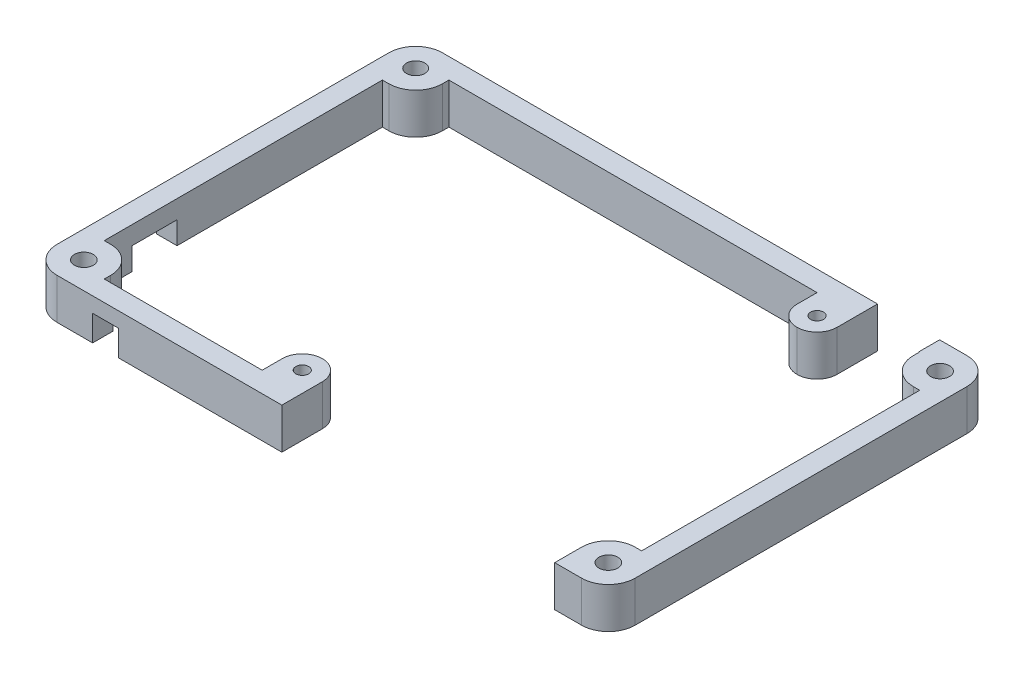
SolidWorks part; units mm, degrees
material "Rubber"
ref_plane "Front" through (0, 0, 0) normal (0, 0, 1) x (1, 0, 0)
ref_plane "Top" through (0, 0, 0) normal (0, 1, 0) x (1, 0, 0)
ref_plane "Right" through (0, 0, 0) normal (1, 0, 0) x (0, 0, -1)
sketch "Sketch1" plane through (0, 0, 0) normal (0, 1, 0) x (1, 0, 0)
  line L0 (-45, 0) -> (45, 0) construction
  line L1 (-45, 30) -> (45, 30) construction
  line L2 (-45, 30) -> (-45, -30) construction
  line L3 (-45, -30) -> (45, -30) construction
  line L4 (45, 30) -> (45, -30) construction
  line L5 (0, -30) -> (0, 30) construction
  line L6 (41.825, 26.825) -> (41.825, -26.825) construction
  line L7 (-41.825, -26.825) -> (41.825, -26.825) construction
  line L8 (-41.825, 26.825) -> (-41.825, -26.825) construction
  line L9 (-41.825, 26.825) -> (41.825, 26.825) construction
  line L10 (40.825, 25.825) -> (40.825, -25.825) construction
  line L11 (-40.825, -25.825) -> (40.825, -25.825) construction
  line L12 (-40.825, 25.825) -> (-40.825, -25.825) construction
  line L13 (-40.825, 25.825) -> (40.825, 25.825) construction
  line L14 (40.825, 21.65) -> (45, 21.65) construction
  line L15 (40.825, -21.65) -> (45, -21.65) construction
  line L16 (36.65, -25.825) -> (36.65, -30) construction
  line L17 (-36.65, -25.825) -> (-36.65, -30) construction
  line L18 (-40.825, -21.65) -> (-45, -21.65) construction
  line L19 (-36.65, 25.825) -> (-36.65, 30) construction
  line L20 (-40.825, 21.65) -> (-45, 21.65) construction
  line L21 (36.65, 25.825) -> (36.65, 30) construction
  line L22 (40.825, -25.825) -> (41.825, -25.825) construction
  circle A0 centre (-40.825, -25.825) radius 1 construction
  circle A1 centre (40.825, -25.825) radius 1 construction
  circle A2 centre (40.825, 25.825) radius 1 construction
  circle A3 centre (-40.825, 25.825) radius 1 construction
  circle A4 centre (40.825, -25.825) radius 4.175 construction
  circle A5 centre (40.825, 25.825) radius 4.175 construction
  circle A6 centre (-40.825, 25.825) radius 4.175 construction
  circle A7 centre (-40.825, -25.825) radius 4.175 construction
  dimension "D1" = 90
  dimension "D2" = 60
  dimension "D4" = 1
  dimension "D3" = 3.175
sketch "Sketch2" plane through (0, 0, 0) normal (0, 1, 0) x (1, 0, 0)
  line L0 (-45, 30) -> (-45, -30) construction
  line L1 (-45, -30) -> (45, -30) construction
  line L2 (45, 30) -> (45, -30) construction
  line L3 (-45, 30) -> (45, 30) construction
  line L4 (40.825, 21.65) -> (45, 21.65) construction
  line L5 (36.65, 25.825) -> (36.65, 30) construction
  line L6 (-36.65, 25.825) -> (-36.65, 30) construction
  line L7 (-40.825, 21.65) -> (-45, 21.65) construction
  line L8 (-36.65, -25.825) -> (-36.65, -30) construction
  line L9 (-40.825, -21.65) -> (-45, -21.65) construction
  line L10 (36.65, -25.825) -> (36.65, -30) construction
  line L11 (40.825, -21.65) -> (45, -21.65) construction
  line L16 (-45, 25.825) -> (-45, -25.825)
  line L17 (-40.825, -30) -> (40.825, -30)
  line L18 (45, 25.825) -> (45, -25.825)
  line L19 (-40.825, 30) -> (40.825, 30)
  line L20 (40.825, 21.65) -> (41.825, 21.65)
  line L21 (36.65, 25.825) -> (36.65, 26.825)
  line L22 (-36.65, 25.825) -> (-36.65, 26.825)
  line L23 (-40.825, 21.65) -> (-41.825, 21.65)
  line L24 (-36.65, -25.825) -> (-36.65, -26.825)
  line L25 (-40.825, -21.65) -> (-41.825, -21.65)
  line L26 (36.65, -25.825) -> (36.65, -26.825)
  line L27 (40.825, -21.65) -> (41.825, -21.65)
  line L28 (41.825, 26.825) -> (41.825, -26.825) construction
  line L29 (-36.65, -26.825) -> (36.65, -26.825)
  line L30 (-41.825, 26.825) -> (41.825, 26.825) construction
  line L31 (-41.825, 26.825) -> (-41.825, -26.825) construction
  line L32 (-36.65, 26.825) -> (36.65, 26.825)
  line L33 (-41.825, 21.65) -> (-41.825, -21.65)
  line L34 (41.825, 21.65) -> (41.825, -21.65)
  line L35 (-41.825, -26.825) -> (41.825, -26.825) construction
  circle A0 centre (40.825, 25.825) radius 4.175 construction
  circle A1 centre (40.825, 25.825) radius 1 construction
  circle A2 centre (-40.825, 25.825) radius 4.175 construction
  circle A3 centre (-40.825, 25.825) radius 1 construction
  circle A4 centre (-40.825, -25.825) radius 4.175 construction
  circle A5 centre (40.825, -25.825) radius 4.175 construction
  arc A6 (45, 25.825) -> (40.825, 30) centre (40.825, 25.825) ccw
  circle A7 centre (40.825, 25.825) radius 1 construction
  arc A8 (-40.825, 30) -> (-45, 25.825) centre (-40.825, 25.825) ccw
  circle A9 centre (-40.825, 25.825) radius 1 construction
  arc A10 (-36.65, -25.825) -> (-40.825, -21.65) centre (-40.825, -25.825) ccw
  arc A11 (40.825, -21.65) -> (36.65, -25.825) centre (40.825, -25.825) ccw
  circle A12 centre (-40.825, -25.825) radius 1 construction
  circle A13 centre (40.825, -25.825) radius 1 construction
  circle A14 centre (-40.825, -25.825) radius 1 construction
  circle A15 centre (40.825, -25.825) radius 1 construction
  arc A16 (-40.825, 21.65) -> (-36.65, 25.825) centre (-40.825, 25.825) ccw
  arc A17 (-45, -25.825) -> (-40.825, -30) centre (-40.825, -25.825) ccw
  arc A18 (40.825, -30) -> (45, -25.825) centre (40.825, -25.825) ccw
  arc A19 (36.65, 25.825) -> (40.825, 21.65) centre (40.825, 25.825) ccw
extrude "Boss-Extrude3" add sketch "Sketch2" along normal blind 6.35
sketch "Sketch3" plane through (0, 0, -30) normal (0, 0, -1) x (-1, 0, 0)
  line L0 (-40.825, 6.35) -> (40.825, 6.35) construction
  line L1 (-36.566, 6.35) -> (-26.9027, 6.35)
  line L2 (-36.566, 6.35) -> (-36.566, 0)
  line L3 (-36.566, 0) -> (-26.9027, 0)
  line L4 (-26.9027, 6.35) -> (-26.9027, 0)
  line L5 (-40.825, 0) -> (40.825, 0) construction
extrude "Cut-Extrude1" cut sketch "Sketch3" against normal up to vertex (3.175 mm away) up to point (36.65, 6.35, -26.825)
sketch "Sketch4" plane through (0, 0, 30) normal (0, 0, 1) x (1, 0, 0)
  line L0 (-40.825, 6.35) -> (40.825, 6.35) construction
  line L1 (36.65, 6.35) -> (-5.825, 6.35)
  line L2 (36.65, 6.35) -> (36.65, 0)
  line L3 (36.65, 0) -> (-5.825, 0)
  line L4 (-5.825, 6.35) -> (-5.825, 0)
  line L5 (-40.825, 0) -> (40.825, 0) construction
  line L6 (-40.825, 6.35) -> (-40.825, 0) construction
  dimension "D1" = 35
extrude "Cut-Extrude2" cut sketch "Sketch4" against normal up to vertex (3.175 mm away) up to point (36.65, 6.35, 26.825)
sketch "Sketch5" plane through (-45, 0, 0) normal (-1, 0, 0) x (0, 0, 1)
  line L0 (13.825, 0) -> (25.825, 0) construction
  line L1 (25.825, 6.35) -> (25.825, 0) construction
  line L3 (17.325, 3.5) -> (10.325, 3.5)
  line L4 (17.325, 3.5) -> (17.325, -3.5)
  line L5 (17.325, -3.5) -> (10.325, -3.5)
  line L6 (10.325, 3.5) -> (10.325, -3.5)
  line L7 (17.325, 3.5) -> (10.325, -3.5) construction
  line L8 (17.325, -3.5) -> (10.325, 3.5) construction
  dimension "D1" = 12
  dimension "D2" = 7
  dimension "D3" = 7
extrude "Cut-Extrude3" cut sketch "Sketch5" against normal up to surface (3.175 mm away) up to face at (-41.825, 3.175, 0)
sketch "Sketch6" plane through (0, 0, 0) normal (0, -1, 0) x (1, 0, 0)
  circle A0 centre (40.825, 25.825) radius 1.4732
  circle A1 centre (40.825, -25.8149) radius 1.4732
  dimension "D1" = 2.9464
  dimension "D2" = 2.9464
extrude "Cut-Extrude4" cut sketch "Sketch6" against normal up to surface (6.35 mm away) up to face at (39.763, 6.35, -3.8321)
sketch "Sketch7" plane through (0, 0, 0) normal (0, -1, 0) x (1, 0, 0)
  circle A0 centre (-40.825, -25.825) radius 1.4224
  circle A1 centre (-40.825, 25.825) radius 1.4732
  circle A2 centre (-40.825, 25.825) radius 1 construction
  dimension "D1" = 2.8448
  dimension "D2" = 2.9464
extrude "Cut-Extrude5" cut sketch "Sketch7" against normal up to surface (6.35 mm away) up to face at (-27.5872, 6.35, 0)
sketch "Sketch8" plane through (0, 0, 26.825) normal (0, 0, -1) x (-1, 0, 0)
  line L0 (36.65, 0) -> (5.825, 0) construction
  line L1 (5.825, 6.35) -> (12.065, 6.35)
  line L2 (5.825, 6.35) -> (5.825, 0)
  line L3 (5.825, 0) -> (12.065, 0)
  line L4 (12.065, 6.35) -> (12.065, 0)
  dimension "D1" = 6.24
extrude "Boss-Extrude4" add sketch "Sketch8" along normal blind 6.24
sketch "Sketch9" plane through (0, 0, -26.825) normal (0, 0, 1) x (1, 0, 0)
  line L0 (26.9027, 0) -> (-36.65, 0) construction
  line L1 (26.9027, 6.35) -> (20.6627, 6.35)
  line L2 (26.9027, 6.35) -> (26.9027, 0)
  line L3 (26.9027, 0) -> (20.6627, 0)
  line L4 (20.6627, 6.35) -> (20.6627, 0)
  dimension "D1" = 6.24
extrude "Boss-Extrude5" add sketch "Sketch9" along normal blind 6.24
sketch "Sketch10" plane through (0, 0, 0) normal (0, -1, 0) x (-1, 0, 0)
  line L0 (-20.6627, 26.825) -> (-26.9027, 20.585) construction
  line L1 (12.065, -26.825) -> (5.825, -20.585) construction
  circle A0 centre (-23.7827, 23.705) radius 1
  circle A1 centre (8.945, -23.705) radius 1
extrude "Cut-Extrude6" cut sketch "Sketch10" against normal through all
fillet "Fillet1" radius 3.12 4 edges at (-12.065, 3.175, 20.585) (-5.825, 3.175, 20.585) (26.9027, 3.175, -20.585) (20.6627, 3.175, -20.585)
sketch "Sketch11" plane through (0, 0, 30) normal (0, 0, 1) x (1, 0, 0)
  line L0 (-40.825, 0) -> (-5.825, 0) construction
  line L1 (-35.285, 4) -> (-31.285, 4)
  line L2 (-35.285, 4) -> (-35.285, 0)
  line L3 (-35.285, 0) -> (-31.285, 0)
  line L4 (-31.285, 4) -> (-31.285, 0)
  line L5 (-35.285, 4) -> (-31.285, 0) construction
  line L6 (-35.285, 0) -> (-31.285, 4) construction
  line L7 (-40.825, 6.35) -> (-40.825, 0) construction
  point P0 (-33.285, 2)
  dimension "D1" = 4
  dimension "D2" = 4
  dimension "D3" = 5.54
extrude "Cut-Extrude7" cut sketch "Sketch11" against normal blind 10
